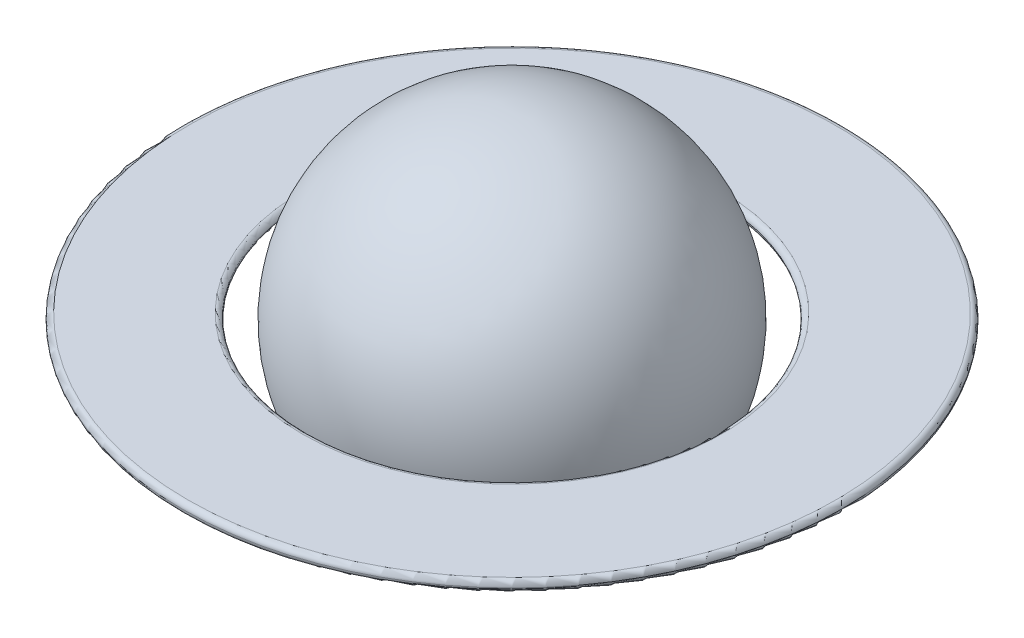
SolidWorks part; units mm, degrees
ref_plane "Plan de face" through (0, 0, 0) normal (0, 0, 1) x (1, 0, 0)
ref_plane "Plan de dessus" through (0, 0, 0) normal (0, 1, 0) x (1, 0, 0)
ref_plane "Plan de droite" through (0, 0, 0) normal (1, 0, 0) x (0, 0, -1)
sketch "Esquisse1" plane through (0, 0, 0) normal (0, 0, 1) x (1, 0, 0)
  line L0 (0, 0) -> (0, 1000) construction
  line L1 (0, 0) -> (0, 1000)
  arc A0 (0, 0) -> (0, 1000) centre (0, 500) ccw
revolve "Révolution1" add sketch "Esquisse1" angle 360 about L0
ref_plane "Plan1" through (0, 500, 0) normal (0, 1, 0) x (1, 0, 0)
sketch "Esquisse2" plane through (0, 500, 0) normal (0, 1, 0) x (1, 0, 0)
  circle A0 centre (0, 0) radius 569.0213
  circle A1 centre (0, 0) radius 916.8574
extrude "Boss.-Extru.1" add sketch "Esquisse2" along normal blind 15 and the other way blind 15 separate body
fillet "Congé1" radius 15 4 edges at (0, 515, 569.0213) (0, 485, 569.0213) (0, 515, 916.8574) (0, 485, 916.8574)
